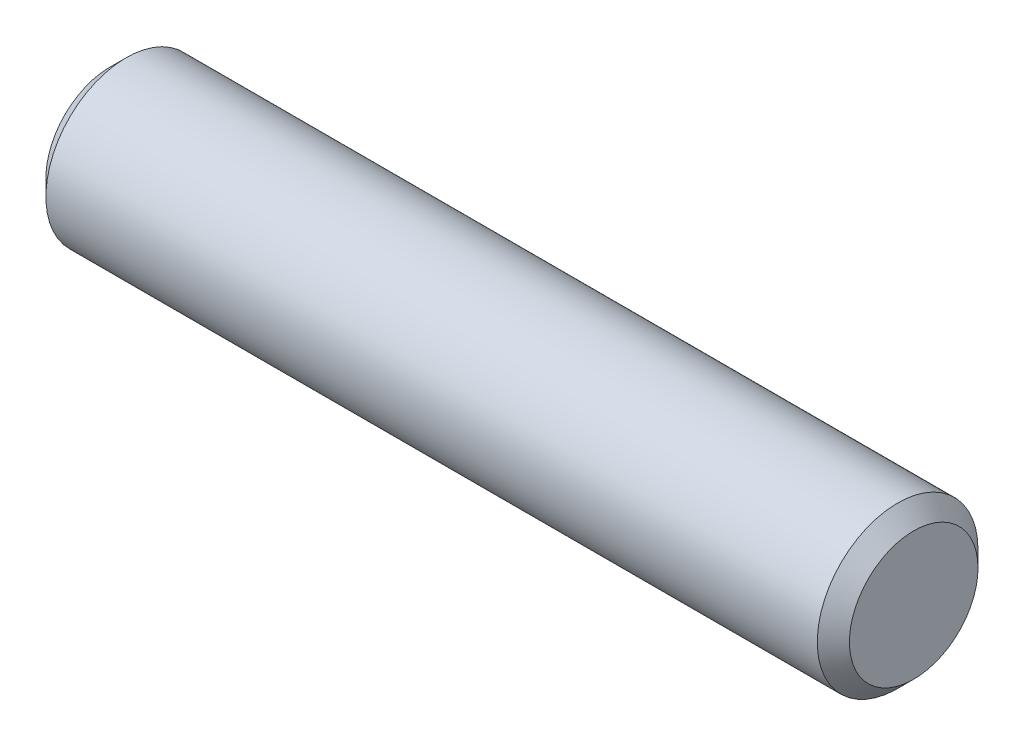
SolidWorks part; units mm, degrees
ref_plane "Front" through (0, 0, 0) normal (0, 0, 1) x (1, 0, 0)
ref_plane "Top" through (0, 0, 0) normal (0, 1, 0) x (1, 0, 0)
ref_plane "Right" through (0, 0, 0) normal (1, 0, 0) x (0, 0, -1)
sketch "Sketch1" plane through (0, 0, 0) normal (0, 0, 1) x (1, 0, 0)
  line L0 (-7.9375, 0) -> (7.9375, 0) construction
  line L1 (7.9375, 1.5875) -> (7.9375, -1.5875) construction
  line L2 (-7.9375, 1.5875) -> (-7.9375, -1.5875) construction
  dimension "Length" = 15.875
  dimension "Diameter" = 3.175
sketch "Sketch2" plane through (0, 0, 0) normal (1, 0, 0) x (0, 0, -1)
  circle A0 centre (0, 0) radius 1.5875
extrude "Extrude1" add sketch "Sketch2" against normal up to vertex (7.9375 mm away) and the other way up to vertex (7.9375 mm away) up to point (-7.9375, 1.5875, 0) other way up to point (7.9375, 1.5875, 0)
chamfer "Chamfer1" distance 0.3175 angle 45 2 edges at (7.9375, 0, -1.5875) (-7.9375, 0, -1.5875)
equation "\"D1@Chamfer1\" = \"Diameter@Sketch1\"*.1"
